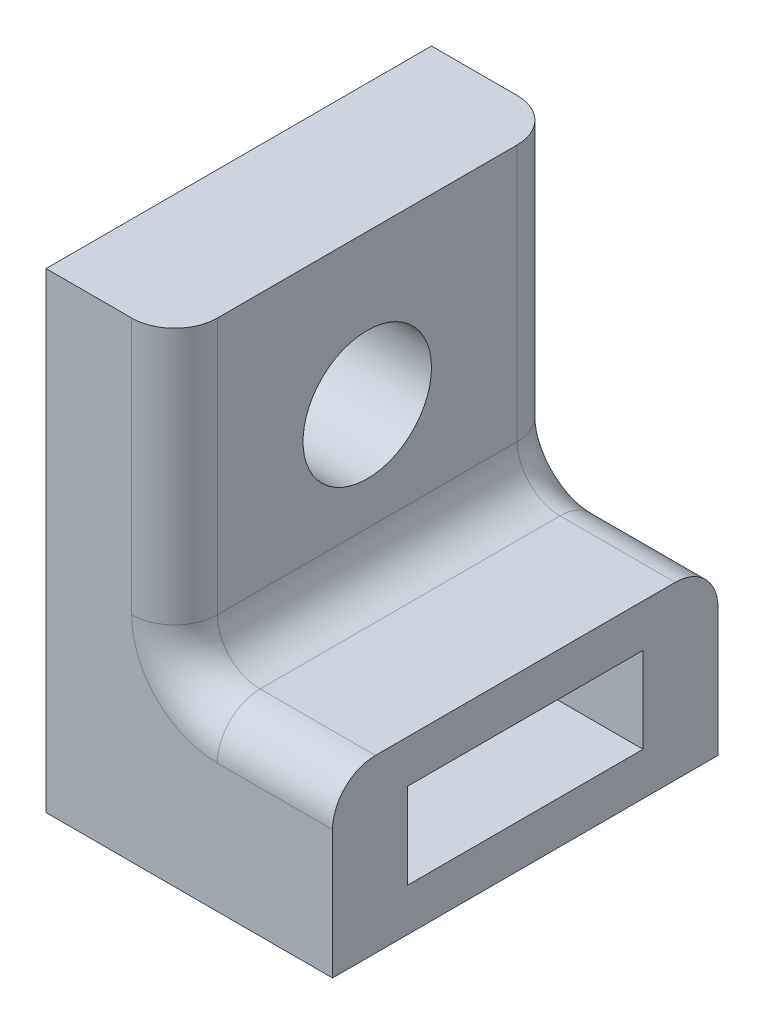
SolidWorks part; units mm, degrees
ref_plane "Front Plane" through (0, 0, 0) normal (0, 0, 1) x (1, 0, 0)
ref_plane "Top Plane" through (0, 0, 0) normal (0, 1, 0) x (1, 0, 0)
ref_plane "Right Plane" through (0, 0, 0) normal (1, 0, 0) x (0, 0, -1)
sketch "Sketch1" plane through (0, 0, 0) normal (0, 0, 1) x (1, 0, 0)
  line L0 (0, 0) -> (-6, 0)
  arc A0 (-6, 0) -> (0, 0) centre (-3, 0) cw
  dimension "D1" = 6
  dimension "D2" = 3
revolve "Revolve1" add sketch "Sketch1" angle 360 about L0
sketch "Sketch2" plane through (0, 0, 0) normal (0, 1, 0) x (1, 0, 0)
  circle A0 centre (-3, 0) radius 1.5
  dimension "D1" = 3
extrude "Cut-Extrude1" cut sketch "Sketch2" against normal blind 10 and the other way blind 10
sketch "Sketch4" plane through (0, 0, 0) normal (0, 1, 0) x (1, 0, 0)
  line L0 (-30.5, 0) -> (-19.7447, 0) construction
  line L1 (2.5, 4.5) -> (-30.5, 4.5)
  line L2 (2.5, 4.5) -> (2.5, -4.5)
  line L3 (2.5, -4.5) -> (-30.5, -4.5)
  line L4 (-30.5, 4.5) -> (-30.5, -4.5)
  line L5 (-7.5, 4.5) -> (-7.5, -4.5) construction
  circle A0 centre (-3, 0) radius 3.5 construction
  dimension "D4" = 4.5
  dimension "D1" = 9
  dimension "D2" = 0
  dimension "D3" = 5.5
  dimension "D5" = 23
extrude "Boss-Extrude1" add sketch "Sketch4" along normal blind 2 and the other way blind 2
sketch "Sketch5" plane through (0, 2, 0) normal (0, 1, 0) x (1, 0, 0)
  circle A0 centre (-3, 0) radius 1.5
extrude "Cut-Extrude2" cut sketch "Sketch5" against normal blind 10 and the other way blind 1.5
sketch "Sketch6" plane through (0, 0, 0) normal (0, 1, 0) x (1, 0, 0)
  line L0 (-3, 3.5) -> (-3, -3.5)
  arc A0 (-3, 3.5) -> (-3, -3.5) centre (-3, 0) ccw
revolve "Cut-Revolve1" cut sketch "Sketch6" angle 360 about L0
sketch "Sketch7" plane through (0, 0, 0) normal (0, 1, 0) x (1, 0, 0)
  line L0 (-3, 3) -> (-3, -3)
  arc A0 (-3, 3) -> (-3, -3) centre (-3, 0) ccw
  dimension "D1" = 6
revolve "Revolve2" add sketch "Sketch7" angle 360 about L0
sketch "Sketch8" plane through (0, 0, 0) normal (0, 1, 0) x (1, 0, 0)
  circle A0 centre (-3, 0) radius 1.5
  dimension "D1" = 3
extrude "Cut-Extrude3" cut sketch "Sketch8" against normal blind 10 and the other way blind 10
sketch "Sketch9" plane through (-30.5, 0, 0) normal (-1, 0, 0) x (0, 0, 1)
  line L1 (-4.5, 2) -> (4.4875, 2)
  line L2 (-4.5, 2) -> (-4.5, 2.7813)
  line L3 (-4.5, 2.7813) -> (4.4875, 2.7813)
  line L4 (4.4875, 2) -> (4.4875, 2.7813)
  line L5 (-4.5, -2) -> (4.4875, -2)
  line L6 (-4.5, -2) -> (-4.5, -3.2255)
  line L7 (-4.5, -3.2255) -> (4.4875, -3.2255)
  line L8 (4.4875, -2) -> (4.4875, -3.2255)
extrude "Cut-Extrude4" cut sketch "Sketch9" against normal blind 46
sketch "Sketch10" plane through (-30.5, 0, 0) normal (-1, 0, 0) x (0, 0, 1)
  line L1 (-2.75, 1) -> (2.75, 1)
  line L2 (-2.75, 1) -> (-2.75, -1)
  line L3 (-2.75, -1) -> (2.75, -1)
  line L4 (2.75, 1) -> (2.75, -1)
  line L5 (-2.75, 1) -> (2.75, -1) construction
  line L6 (-2.75, -1) -> (2.75, 1) construction
  point P0 (0, 0)
  dimension "D1" = 5.5
  dimension "D2" = 2
extrude "Cut-Extrude5" cut sketch "Sketch10" against normal blind 30
sketch "Sketch11" plane through (0, 2, 0) normal (0, 1, 0) x (1, 0, 0)
  line L0 (-30.5, -4.5) -> (2.5, -4.5) construction
  line L1 (-30.5, 4.5) -> (-27.5, 4.5)
  line L2 (-30.5, 4.5) -> (-30.5, -4.5)
  line L3 (-30.5, -4.5) -> (-27.5, -4.5)
  line L4 (-27.5, 4.5) -> (-27.5, -4.5)
  dimension "D1" = 3
extrude "Boss-Extrude2" add sketch "Sketch11" along normal blind 7
sketch "Sketch12" plane through (-27.5, 0, 0) normal (1, 0, 0) x (0, 0, -1)
  line L0 (-4.5, 9) -> (4.5, 9) construction
  circle A0 centre (0, 5.5) radius 1.5
  dimension "D1" = 3
  dimension "D2" = 3.5
extrude "Cut-Extrude6" cut sketch "Sketch12" against normal blind 7
fillet "Fillet1" radius 1 1 edges at (2.5, 0, -4.5)
fillet "Fillet2" radius 1 1 edges at (2.5, 0, 4.5)
fillet "Fillet3" radius 1 1 edges at (-27.5, 2, 0)
fillet "Fillet4" radius 1 9 edges at (-27.5, 6, 4.5) (-27.2071, 2.2929, 4.5) (-12.5, 2, 4.5) (2.2071, 2, 4.2071) (2.5, 2, 0) (2.2071, 2, -4.2071) (-27.5, 6, -4.5) (-27.2071, 2.2929, -4.5) (-12.5, 2, -4.5)
sketch "Sketch13" plane through (0, 2, 0) normal (0, 1, 0) x (1, 0, 0)
  line L1 (-23.8113, 5.7241) -> (4.2546, 5.7241)
  line L2 (-23.8113, 5.7241) -> (-23.8113, -7.5699)
  line L3 (-23.8113, -7.5699) -> (4.2546, -7.5699)
  line L4 (4.2546, 5.7241) -> (4.2546, -7.5699)
extrude "Cut-Extrude7" cut sketch "Sketch13" against normal blind 10
